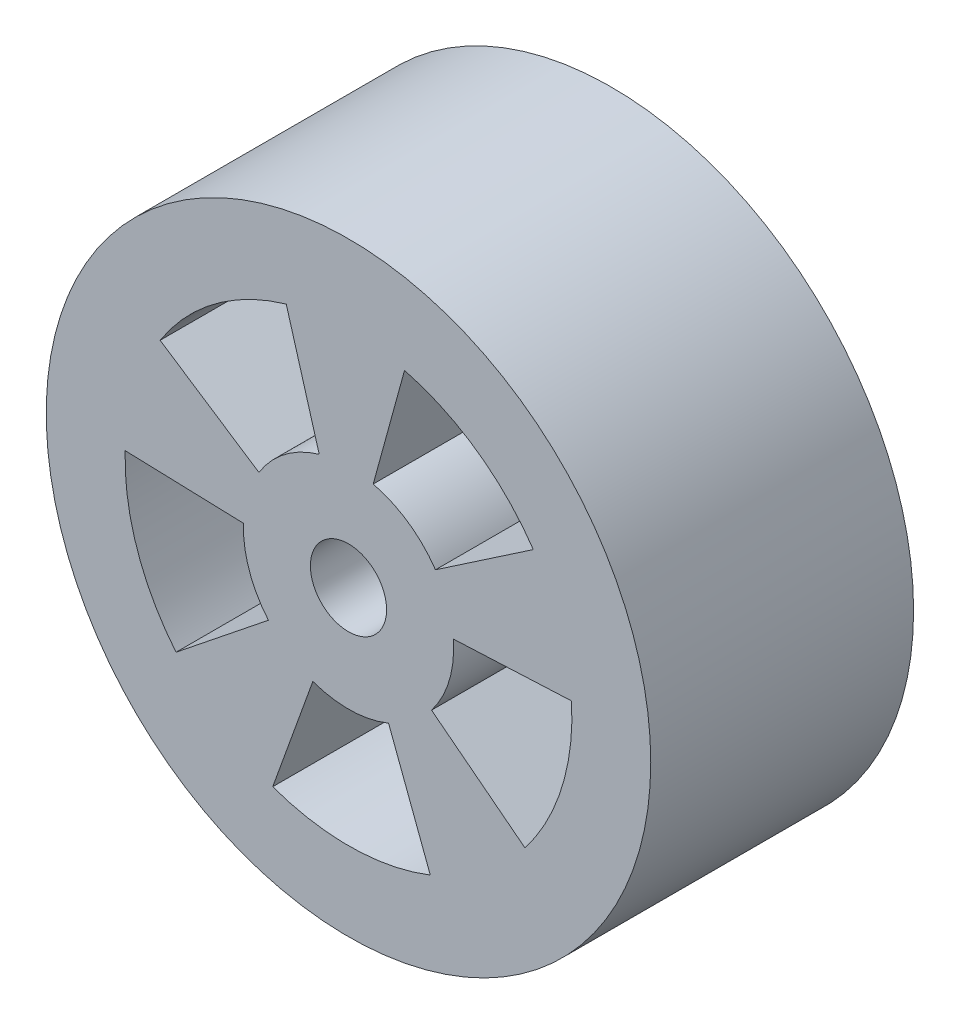
SolidWorks part; units mm, degrees
ref_plane "Front Plane" through (0, 0, 0) normal (0, 0, 1) x (1, 0, 0)
ref_plane "Top Plane" through (0, 0, 0) normal (0, 1, 0) x (1, 0, 0)
ref_plane "Right Plane" through (0, 0, 0) normal (1, 0, 0) x (0, 0, -1)
sketch "Sketch1" plane through (0, 0, 0) normal (0, 0, 1) x (1, 0, 0)
  circle A0 centre (0, 0) radius 11.5
  dimension "D1" = 23
extrude "Boss-Extrude1" add sketch "Sketch1" along normal blind 10
sketch "Sketch2" plane through (0, 0, 10) normal (0, 0, 1) x (1, 0, 0)
  circle A0 centre (0, 0) radius 8.5
  dimension "D1" = 17
extrude "Cut-Extrude2" cut sketch "Sketch2" against normal blind 10
sketch "Sketch4" plane through (0, 0, 0) normal (0, 0, 1) x (1, 0, 0)
  circle A0 centre (0, 0) radius 4
  dimension "D1" = 8
extrude "Boss-Extrude2" add sketch "Sketch4" along normal blind 10 separate body
sketch "Sketch6" plane through (0, 0, 0) normal (0, 0, 1) x (1, 0, 0)
  line L0 (-1.1144, 3.8416) -> (-2.3682, 8.1634)
  line L1 (0.9403, 3.8879) -> (2.1318, 8.2283)
  circle A0 centre (0, 0) radius 4 construction
  circle A1 centre (0, 0) radius 8.5 construction
  arc A2 (-2.3682, 8.1634) -> (2.1318, 8.2283) centre (0, 0) cw
  arc A3 (0.9403, 3.8879) -> (-1.1144, 3.8416) centre (0, 0) ccw
  dimension "D1" = 4.5
  dimension "D2" = 2.0553
extrude "Boss-Extrude3" add sketch "Sketch6" along normal blind 10
pattern_circular "CirPattern1" count 5 every 72 about axis through (0, 0, 10) along (0, 0, 1) of "Boss-Extrude3"
sketch "Sketch7" plane through (0, 0, 10) normal (0, 0, 1) x (1, 0, 0)
  circle A0 centre (0, 0) radius 1.45
  dimension "D1" = 2.9
extrude "Cut-Extrude3" cut sketch "Sketch7" against normal blind 10
sketch "Sketch8" plane through (0, 0, 0) normal (0, 0, -1) x (-1, 0, 0)
  circle A0 centre (0, 0) radius 1.75
  dimension "D1" = 3.5
extrude "Boss-Extrude4" add sketch "Sketch8" along normal blind 2
sketch "Sketch9" plane through (0, 0, -2) normal (0, 0, -1) x (-1, 0, 0)
  circle A0 centre (0, 0) radius 1.45
  dimension "D1" = 2.9
extrude "Cut-Extrude4" cut sketch "Sketch9" against normal blind 2
fillet "Fillet1" radius 2.25 1 edges at (1.75, 0, 0)
